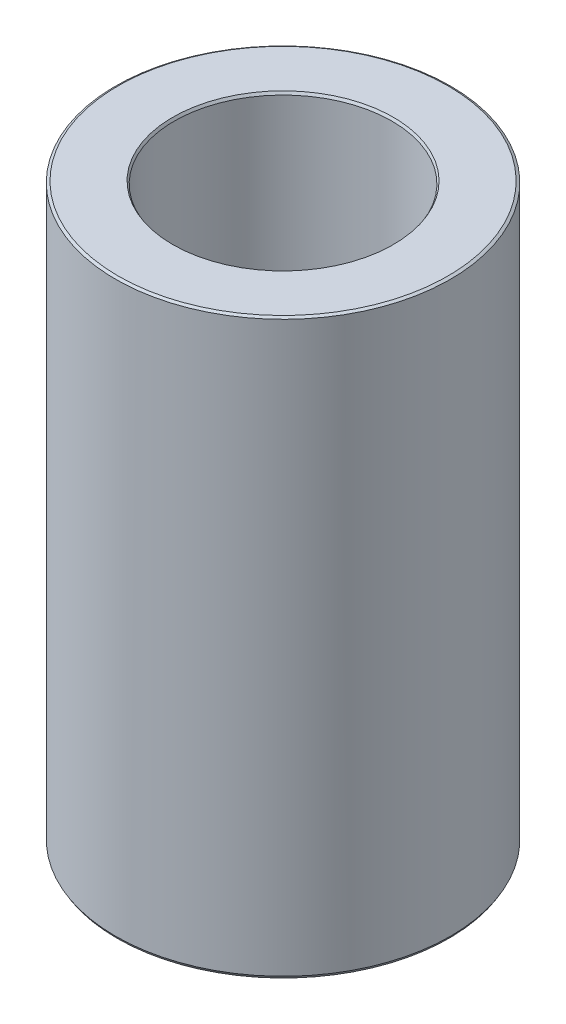
SolidWorks part; units mm, degrees
ref_plane "Front Plane" through (0, 0, 0) normal (0, 0, 1) x (1, 0, 0)
ref_plane "Top Plane" through (0, 0, 0) normal (0, 1, 0) x (1, 0, 0)
ref_plane "Right Plane" through (0, 0, 0) normal (1, 0, 0) x (0, 0, -1)
sketch "Sketch1" plane through (0, 0, 0) normal (0, 1, 0) x (1, 0, 0)
  circle A0 centre (0, 0) radius 50
  dimension "SLEEVE_OD" = 100
extrude "Boss-Extrude1" add sketch "Sketch1" along normal blind 171.1337
sketch "Sketch2" plane through (0, 0, 0) normal (0, 1, 0) x (1, 0, 0)
  circle A0 centre (0, 0) radius 32.5023
  dimension "BORE_D" = 65.0047
extrude "Cut-Extrude1" cut sketch "Sketch2" along normal through all
chamfer "Chamfer1" distance 0.447 angle 60 4 edges at (0, 171.1337, 32.5023) (0, 0, 32.5023) (0, 0, 50) (0, 171.1337, 50) first distance on face at (0, 171.1337, 32.5023) first distance on face at (0, 0, 32.5023) first distance on face at (0, 171.1337, 50)
